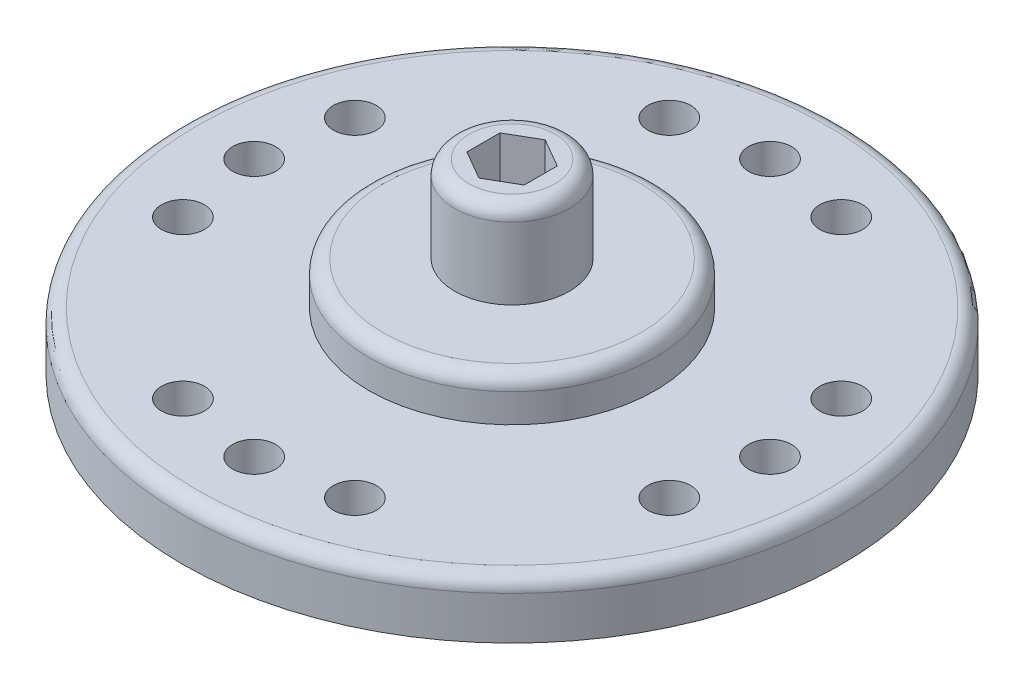
SolidWorks part; units mm, degrees
material "Comercialmente puro CP-Ti UNS R50400 (SS)"
ref_plane "Alzado" through (0, 0, 0) normal (0, 0, 1) x (1, 0, 0)
ref_plane "Planta" through (0, 0, 0) normal (0, 1, 0) x (1, 0, 0)
ref_plane "Vista lateral" through (0, 0, 0) normal (1, 0, 0) x (0, 0, -1)
sketch "Croquis1" plane through (0, 0, 0) normal (0, 1, 0) x (1, 0, 0)
  line L0 (-17.8, 0) -> (17.8, 0) construction
  line L1 (-17.8, -22.5) -> (17.8, -22.5) construction
  line L2 (17.8, -17.3) -> (17.8, 17.3)
  line L3 (11.8, 25.3) -> (-11.8, 25.3)
  line L4 (-17.8, -17.3) -> (-17.8, 17.3)
  line L5 (0, 25.3) -> (0, -25.3) construction
  line L6 (15, 25.3) -> (15, -22.1056) construction
  line L7 (-11.8, 25.3) -> (11.8, 25.3)
  line L8 (-12.2, 23.8) -> (-12.2, -18.2)
  line L9 (-10.7, -19.7) -> (10.7, -19.7)
  line L10 (12.2, 23.8) -> (12.2, -18.2)
  line L11 (12.2, 19.8) -> (17.8, 19.8)
  line L12 (17.4641, 18.4094) -> (13.4641, 24.4094)
  line L13 (1, 13.8774) -> (0, 14.4547)
  line L14 (0, 14.4547) -> (-1, 13.8774)
  line L15 (-1, 13.8774) -> (-1, 12.7226)
  line L16 (-1, 12.7226) -> (0, 12.1453)
  line L17 (0, 12.1453) -> (1, 12.7226)
  line L18 (1, 12.7226) -> (1, 13.8774)
  line L19 (-17.4641, 18.4094) -> (-13.4641, 24.4094)
  line L20 (17.4641, -18.4094) -> (13.4641, -24.4094)
  line L21 (-17.4641, -18.4094) -> (-13.4641, -24.4094)
  line L22 (-11.8, -25.3) -> (11.8, -25.3)
  line L23 (-10.7, 25.3) -> (10.7, 25.3)
  line L24 (12.2, 15.8) -> (17.8, 15.8)
  circle A0 centre (0, 13.3) radius 11.5
  circle A1 centre (0, 13.3) radius 2
  circle A2 centre (0, 13.3) radius 9 construction
  circle A3 centre (3, 21.7853) radius 0.75
  circle A4 centre (0, 13.3) radius 5
  circle A5 centre (0, 22.3) radius 0.75
  circle A6 centre (-3, 21.7853) radius 0.75
  circle A7 centre (15, 17.8) radius 1
  circle A8 centre (15, 0.8) radius 1
  circle A9 centre (15, -16.2) radius 1
  circle A10 centre (-8.5, -22.5) radius 1
  circle A11 centre (8.5, -22.5) radius 1
  circle A12 centre (-15, -16.2) radius 1
  circle A13 centre (-15, 0.8) radius 1
  circle A14 centre (-15, 17.8) radius 1
  circle A15 centre (0, 13.3) radius 1 construction
  arc A16 (13.4641, 24.4094) -> (11.8, 25.3) centre (11.8, 23.3) ccw
  arc A17 (17.4641, 18.4094) -> (17.8, 17.3) centre (15.8, 17.3) cw
  arc A18 (-17.4641, 18.4094) -> (-17.8, 17.3) centre (-15.8, 17.3) ccw
  arc A19 (-13.4641, 24.4094) -> (-11.8, 25.3) centre (-11.8, 23.3) cw
  arc A20 (13.4641, -24.4094) -> (11.8, -25.3) centre (11.8, -23.3) cw
  arc A21 (17.4641, -18.4094) -> (17.8, -17.3) centre (15.8, -17.3) ccw
  arc A22 (-13.4641, -24.4094) -> (-11.8, -25.3) centre (-11.8, -23.3) ccw
  arc A23 (-17.4641, -18.4094) -> (-17.8, -17.3) centre (-15.8, -17.3) cw
  arc A24 (10.7, -19.7) -> (12.2, -18.2) centre (10.7, -18.2) ccw
  arc A25 (-12.2, -18.2) -> (-10.7, -19.7) centre (-10.7, -18.2) ccw
  arc A26 (-12.2, 23.8) -> (-10.7, 25.3) centre (-10.7, 23.8) cw
  arc A27 (10.7, 25.3) -> (12.2, 23.8) centre (10.7, 23.8) cw
  point P1 (0, 25.3)
  point P4 (0, 25.3)
  point P56 (12.8704, 25.3)
  point P59 (17.8, 17.9056)
  dimension "D5" = 23
  dimension "D7" = 1.5
  dimension "D8" = 2
  dimension "D9" = 12.5
  dimension "D10" = 17
  dimension "D11" = 18
  dimension "D12" = 3
  dimension "D13" = 10
  dimension "D14" = 4
  dimension "D17" = 2
  dimension "D18" = 2
  dimension "D21" = 4
  dimension "D16" = 1.5
  dimension "D3" = 35.6
  dimension "D4" = 50.6
  dimension "D6" = 12
  dimension "D15" = 17
  dimension "D19" = 45
  dimension "D20" = 24.4
  dimension "D22" = 2
  dimension "D23" = 4
  dimension "D24" = 6
  dimension "D25" = 4.5
extrude "Saliente-Extruir1" add sketch "Croquis1" along normal blind 2 contours A0
extrude "Cortar-Extruir2" cut sketch "Croquis1<9>" along normal blind 3 contours A5 | A3 | A6 region at (3, 0, -21.7853) region at (0, 0, -22.3)
sketch "Croquis1<9>" plane through (0, 0, 0) normal (0, 1, 0) x (1, 0, 0) same geometry as "Croquis1"
pattern_circular "MatrizC2" count 4 over 360 about axis through (0, 2, -13.3) along (0, 1, 0) of "Cortar-Extruir2"
extrude "Saliente-Extruir2" add sketch "Croquis1<11>" along normal blind 1.5 from surface contours A4 starting at face at (8.4853, 2, -15.55)
sketch "Croquis1<11>" plane through (0, 0, 0) normal (0, 1, 0) x (1, 0, 0) same geometry as "Croquis1"
extrude "Saliente-Extruir3" add sketch "Croquis1<12>" along normal blind 3 from surface contours A1 L18 L17 L16 L15 L14 L13 region at (-1.9434, 0, -13.3) starting at face at (0, 3.5, -8.3)
sketch "Croquis1<12>" plane through (0, 0, 0) normal (0, 1, 0) x (1, 0, 0) same geometry as "Croquis1"
fillet "Redondeo1" radius 0.5 3 edges at (0, 6.5, -11.3) (0, 3.5, -8.3) (0, 2, -1.8)
extrude "Saliente-Extruir4" add sketch "Croquis1<13>" against normal blind 1 contours A4 A1 region at (-4.8586, 0, -13.3)
sketch "Croquis1<13>" plane through (0, 0, 0) normal (0, 1, 0) x (1, 0, 0) same geometry as "Croquis1"
